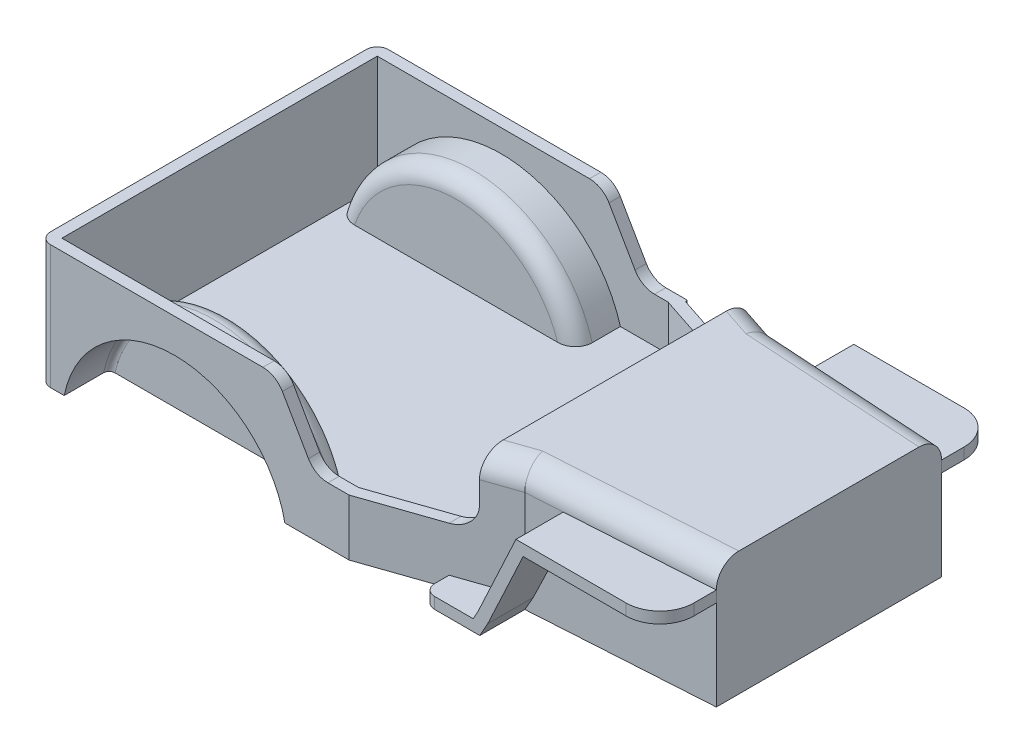
SolidWorks part; units mm, degrees
ref_plane "Front Plane" through (0, 0, 0) normal (0, 0, 1) x (1, 0, 0)
ref_plane "Top Plane" through (0, 0, 0) normal (0, 1, 0) x (1, 0, 0)
ref_plane "Right Plane" through (0, 0, 0) normal (1, 0, 0) x (0, 0, -1)
sketch "Sketch1" plane through (0, 0, 0) normal (0, 1, 0) x (1, 0, 0)
  line L1 (0, -140) -> (0, 140)
  line L2 (10, 150) -> (275, 150)
  line L3 (275, 150) -> (276.0381, 147.9239)
  line L4 (276.0381, 147.9239) -> (391.0381, 110)
  line L5 (391.0381, 110) -> (551.0381, 100)
  line L6 (551.0381, 100) -> (551.0381, -100)
  line L7 (391.0381, -110) -> (551.0381, -100)
  line L8 (275, -150) -> (391.0381, -110)
  line L9 (10, -150) -> (275, -150)
  arc A0 (10, -150) -> (0, -140) centre (10, -140) cw
  arc A1 (10, 150) -> (0, 140) centre (10, 140) ccw
  point P0 (276.0381, -150)
  point P14 (335.5096, 110)
  point P17 (0, -150)
  point P20 (0, 150)
  dimension "D7" = 10
  dimension "D1" = 300
  dimension "D2" = 200
  dimension "D3" = 220
  dimension "D4" = 160
  dimension "D5" = 275
  dimension "D6" = 115
extrude "Boss-Extrude1" add sketch "Sketch1" against normal blind 10
sketch "Sketch2" plane through (0, 0, 0) normal (0, 1, 0) x (1, 0, 0)
  line L0 (361.0381, 119.8932) -> (361.0381, -120.3414)
  line L9 (391.0381, -110) -> (551.0381, -100)
  line L10 (551.0381, -100) -> (551.0381, 100)
  line L11 (551.0381, 100) -> (391.0381, 110)
  line L12 (391.0381, 110) -> (276.0381, 147.9239)
  line L13 (276.0381, 147.9239) -> (275, 150)
  line L14 (275, 150) -> (10, 150)
  line L15 (0, 140) -> (0, -140)
  line L16 (10, -150) -> (275, -150)
  line L17 (275, -150) -> (391.0381, -110)
  line L18 (391.0381, -110) -> (551.0381, -100)
  line L19 (551.0381, -100) -> (551.0381, 100)
  line L20 (551.0381, 100) -> (391.0381, 110)
  line L21 (391.0381, 110) -> (361.0381, 119.8932)
  line L22 (276.0381, 147.9239) -> (275, 150)
  line L23 (275, 150) -> (10, 150)
  line L24 (0, 140) -> (0, -140)
  line L25 (10, -150) -> (275, -150)
  line L26 (361.0381, -120.3414) -> (391.0381, -110)
  arc A2 (10, 150) -> (0, 140) centre (10, 140) ccw
  arc A3 (0, -140) -> (10, -150) centre (10, -140) ccw
  arc A4 (10, 150) -> (0, 140) centre (10, 140) ccw
  arc A5 (0, -140) -> (10, -150) centre (10, -140) ccw
  line M13 (391.0381, -110) -> (551.0381, -100)
  line M14 (551.0381, -100) -> (551.0381, 100)
  line M15 (551.0381, 100) -> (391.0381, 110)
  line M16 (391.0381, 110) -> (276.0381, 147.9239)
  line M23 (275, -150) -> (391.0381, -110)
  dimension "D2" = 190
  dimension "D1" = 0
extrude "Boss-Extrude2" add sketch "Sketch2" along normal blind 100 contours L0 M16 M23 M13 M14 M15 region at (453.7552, 0, 0.0194)
fillet "Fillet1" radius 20 4 edges at (376.0381, 100, -114.9466) (376.0381, 100, 115.1707) (471.0381, 100, -105) (471.0381, 100, 105)
shell "Shell1" thickness 10 removed face at (361.0381, 61.3807, 0.2115)
sketch "Sketch5" plane through (0, 0, 0) normal (0, 1, 0) x (1, 0, 0)
  line L0 (10, 140) -> (10, -140)
  line L1 (10, -140) -> (273.3248, -140)
  line L2 (273.3248, -140) -> (351.0381, -113.2111)
  line L3 (351.0381, -113.2111) -> (351.0381, -102.6336)
  line L4 (351.0381, -102.6336) -> (361.0381, -102.6336)
  line L5 (361.0381, -102.6336) -> (361.0381, -109.764)
  line L6 (531.0381, -81.211) -> (531.0381, 81.211)
  line L8 (361.0381, 98.8337) -> (351.0381, 102.1315)
  line L9 (351.0381, 102.1315) -> (351.0381, 112.6612)
  line L10 (351.0381, 112.6612) -> (268.9546, 139.7301)
  line L11 (268.9546, 139.7301) -> (268.8197, 140)
  line L12 (268.8197, 140) -> (10, 140)
  line L13 (361.0381, 109.3635) -> (361.0381, 119.8932)
  line L14 (361.0381, 119.8932) -> (276.0381, 147.9239)
  line L15 (276.0381, 147.9239) -> (275, 150)
  line L16 (275, 150) -> (10, 150)
  line L17 (0, 140) -> (0, -140)
  line L18 (10, -150) -> (275, -150)
  line L19 (275, -150) -> (361.0381, -120.3414)
  line L20 (361.0381, -120.3414) -> (361.0381, -109.764)
  line L21 (361.0381, -109.764) -> (389.061, -100.1041)
  line L22 (389.061, -100.1041) -> (541.0381, -90.6055)
  line L23 (541.0381, -90.6055) -> (541.0381, 90.6055)
  line L24 (541.0381, 90.6055) -> (389.1291, 100.0998)
  line L25 (389.1291, 100.0998) -> (361.0381, 109.3635)
  line L26 (361.0381, 109.3635) -> (361.0381, 119.8932)
  line L27 (361.0381, 119.8932) -> (276.0381, 147.9239)
  line L28 (276.0381, 147.9239) -> (275, 150)
  line L29 (275, 150) -> (10, 150)
  line L30 (0, 140) -> (0, -140)
  line L31 (10, -150) -> (275, -150)
  line L32 (275, -150) -> (361.0381, -120.3414)
  line L33 (361.0381, -120.3414) -> (361.0381, -109.764)
  line L34 (361.0381, -109.764) -> (389.061, -100.1041)
  line L36 (541.0381, -90.6055) -> (541.0381, 90.6055)
  line L40 (361.0381, 109.3635) -> (361.0381, 98.8337)
  line L42 (387.2202, 90.1996) -> (351.0381, 102.1315) construction
  line L43 (531.0381, 81.211) -> (387.2202, 90.1996) construction
  line L44 (541.0381, 90.6055) -> (389.1291, 100.0998) construction
  line L45 (389.1291, 100.0998) -> (361.0381, 109.3635) construction
  line L46 (389.061, -100.1041) -> (541.0381, -90.6055) construction
  line L47 (387.0839, -90.2081) -> (531.0381, -81.211) construction
  line L48 (351.0381, -102.6336) -> (387.0839, -90.2081) construction
  arc A0 (10, -140) -> (10, -140) centre (10, -140) ccw
  arc A1 (10, 140) -> (10, 140) centre (10, 140) ccw
  arc A2 (10, 150) -> (0, 140) centre (10, 140) ccw
  arc A3 (0, -140) -> (10, -150) centre (10, -140) ccw
  arc A4 (10, 150) -> (0, 140) centre (10, 140) ccw
  arc A5 (0, -140) -> (10, -150) centre (10, -140) ccw
  dimension "D1" = 0
  dimension "D2" = 10
extrude "Boss-Extrude3" add sketch "Sketch5" along normal blind 100 contours L5 L4 L3 L2 L1 A0 L0 A1 L12 L11 L10 L9 L8 L40 L26 L27 L28 L29 A4 L30 A5 L31 L32 L33
sketch "Sketch6" plane through (0, 0, 0) normal (0, 0, 1) x (1, 0, 0)
  line L0 (210, 100) -> (361.0381, 100)
  line L1 (10, 100) -> (275, 100) construction
  line L2 (361.0381, 100) -> (361.0381, 40)
  line L3 (361.0381, 40) -> (244.641, 40)
  line L4 (244.641, 40) -> (210, 100)
  line L5 (275, -10) -> (391.0381, -10) construction
  line L6 (0, -10) -> (0, 100) construction
  point P5 (302.8395, 40)
  point P11 (333.019, -10)
  dimension "D1" = 120
  dimension "D2" = 50
  dimension "D3" = 210
extrude "Cut-Extrude1" cut sketch "Sketch6" against normal mid plane 420
fillet "Fillet2" radius 20 6 edges at (351.0381, 40, -107.3963) (351.0381, 40, 107.9224) (244.641, 40, -145) (244.641, 40, 145) (210, 100, 145) (210, 100, -145)
fillet "Fillet3" radius 20 2 edges at (361.0381, 40, 115.0527) (361.0381, 40, -114.6283)
sketch "Sketch7" plane through (0, 0, -140) normal (0, 0, 1) x (1, 0, 0)
  line L0 (10, -10) -> (275, -10) construction
  line L1 (11.8335, -10) -> (22.0204, -10)
  line L2 (217.9796, -10) -> (228.1665, -10)
  arc A0 (11.8335, -10) -> (228.1665, -10) centre (120, -30) cw
  arc A1 (22.0204, -10) -> (217.9796, -10) centre (120, -30) cw
  dimension "D1" = 120
  dimension "D3" = 110
  dimension "D4" = 100
  dimension "D2" = 20
extrude "Boss-Extrude4" add sketch "Sketch7" along normal blind 40
sketch "Sketch8" plane through (0, 0, -100) normal (0, 0, 1) x (1, 0, 0)
  line L0 (24.6061, 0) -> (215.3939, 0)
  arc A0 (215.3939, 0) -> (24.6061, 0) centre (120, -30) ccw construction
  arc A1 (215.3939, 0) -> (24.6061, 0) centre (120, -30) ccw
extrude "Boss-Extrude5" add sketch "Sketch8" against normal blind 10
sketch "Sketch9" plane through (0, 0, -150) normal (0, 0, -1) x (-1, 0, 0)
  line L0 (-275, -10) -> (-10, -10) construction
  line L1 (-217.9796, -10) -> (-22.0204, -10)
  line L2 (0, -10) -> (0, 100) construction
  arc A0 (-217.9796, -10) -> (-22.0204, -10) centre (-120, -30) cw
  dimension "D1" = 20
  dimension "D3" = 100
  dimension "D2" = 120
extrude "Cut-Extrude2" cut sketch "Sketch9" against normal blind 40
fillet "Fillet4" radius 5 1 edges at (120, 70, -110)
fillet "Fillet5" radius 15 1 edges at (120, 80, -100)
mirror "Mirror1" about plane through (0, 0, 0) normal (0, 0, 1) of "Cut-Extrude2"
mirror "Mirror2" about plane through (0, 0, 0) normal (0, 0, 1) of "Boss-Extrude5", "Boss-Extrude4"
fillet "Fillet6" radius 15 1 edges at (120, 80, 100)
fillet "Fillet7" radius 5 1 edges at (120, 70, 110)
sketch "Sketch10" plane through (0, 0, 150) normal (0, 0, 1) x (1, 0, 0)
  line L0 (551.0381, 70) -> (429.5147, 70)
  line L1 (551.0381, -10) -> (551.0381, 80) construction
  line L2 (429.5147, 70) -> (398.1097, 2.6518)
  line L3 (398.1097, 2.6518) -> (391.0381, -10)
  line L4 (391.0381, -10) -> (341.0381, -10)
  line L5 (275, -10) -> (391.0381, -10) construction
  line L6 (551.0381, 80) -> (423.144, 80)
  line L7 (423.144, 80) -> (389.2017, 7.2105)
  line L8 (389.2017, 7.2105) -> (385.1714, 0)
  line L9 (385.1714, 0) -> (341.0381, 0)
  line L10 (341.0381, 0) -> (341.0381, -10)
  line L11 (551.0381, 80) -> (551.0381, 70)
  dimension "D1" = 210
  dimension "D2" = 50
  dimension "D3" = 115
  dimension "D4" = 80
  dimension "D5" = 10
extrude "Boss-Extrude7" add sketch "Sketch10" against normal up to next separate body
fillet "Fillet8" radius 10 1 edges at (341.0381, -5, 150)
fillet "Fillet9" radius 30 1 edges at (551.0381, 75, 150)
mirror "Mirror4" about plane through (0, 0, 0) normal (0, 0, 1) of bodies 113
